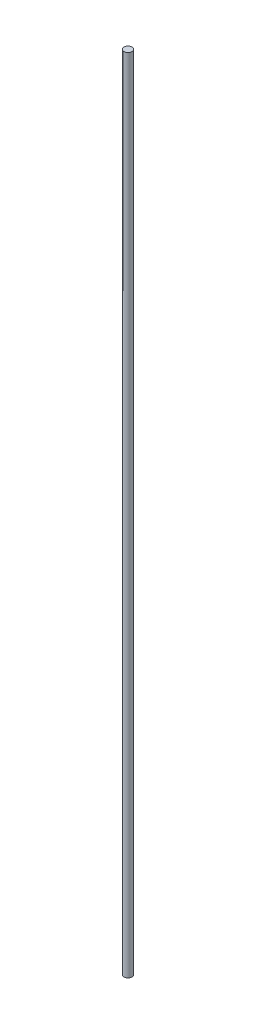
SolidWorks part; units mm, degrees
ref_plane "Front Plane" through (0, 0, 0) normal (0, 0, 1) x (1, 0, 0)
ref_plane "Top Plane" through (0, 0, 0) normal (0, 1, 0) x (1, 0, 0)
ref_plane "Right Plane" through (0, 0, 0) normal (1, 0, 0) x (0, 0, -1)
sketch "Sketch3" plane through (0, 0, 0) normal (0, 1, 0) x (1, 0, 0)
  circle A0 centre (0, 0) radius 2.5
  dimension "D1" = 5
extrude "Boss-Extrude1" add sketch "Sketch3" along normal mid plane 500
